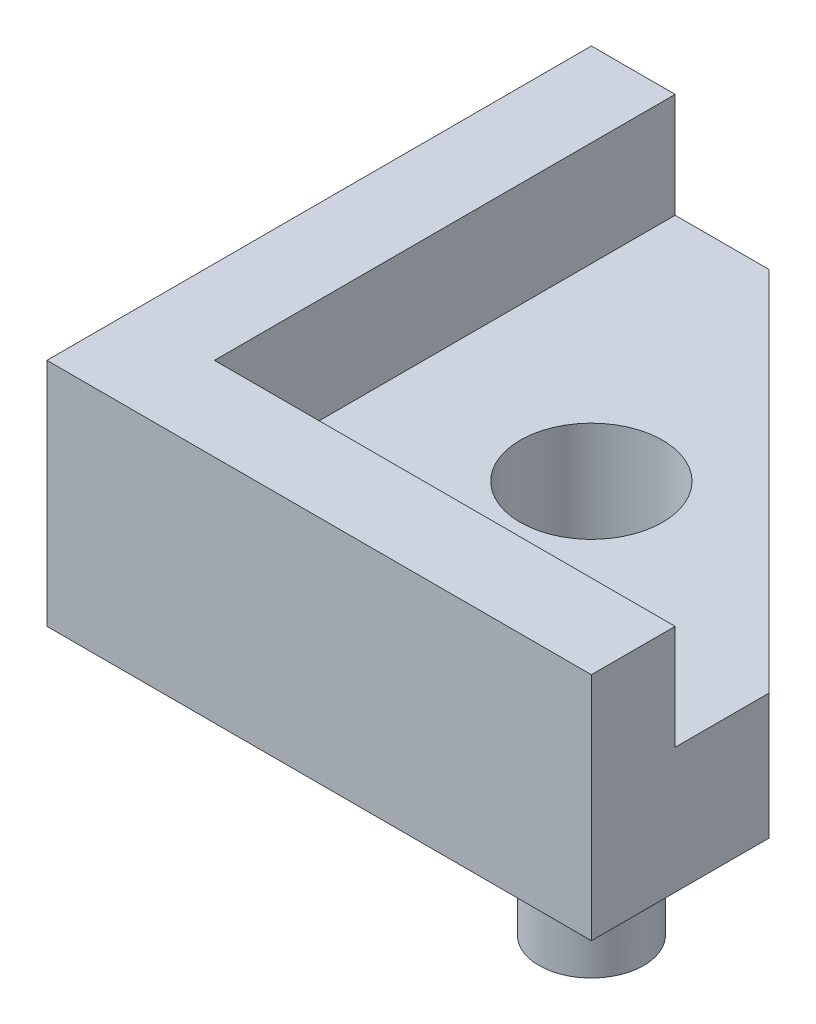
SolidWorks part; units mm, degrees
ref_plane "Front Plane" through (0, 0, 0) normal (0, 0, 1) x (1, 0, 0)
ref_plane "Top Plane" through (0, 0, 0) normal (0, 1, 0) x (1, 0, 0)
ref_plane "Right Plane" through (0, 0, 0) normal (1, 0, 0) x (0, 0, -1)
sketch "Board" plane through (0, 0, 0) normal (0, 1, 0) x (1, 0, 0)
  line L8 (0, 0) -> (85, 0) construction
  line L9 (0, 0) -> (0, 85) construction
  line L10 (0, 85) -> (85, 85) construction
  line L11 (85, 0) -> (85, 85) construction
  circle A1 centre (4, 4) radius 1.6 construction
  point P10 (8.1166, 0)
  dimension "D3" = 3.2
  dimension "D1" = 85
  dimension "D2" = 85
  dimension "D4" = 4
  dimension "D5" = 4
sketch "Sketch3" plane through (0, 0, 0) normal (0, 1, 0) x (1, 0, 0)
  line L0 (-2.5, 10.5) -> (-2.5, -2.5)
  line L1 (-2.5, -2.5) -> (10.5, -2.5)
  line L2 (10.5, -2.5) -> (10.5, 1.7426)
  line L3 (10.5, 1.7426) -> (1.7426, 10.5)
  line L4 (1.7426, 10.5) -> (-2.5, 10.5)
  line L5 (0, 0) -> (0, 85) construction
  line L6 (0, 0) -> (85, 0) construction
  point P2 (-2.7933, 11.3617)
  point P11 (-2, 13)
  dimension "D1" = 2.5
  dimension "D2" = 2.5
  dimension "D3" = 45
  dimension "D4" = 13
  dimension "D5" = 13
  dimension "D6" = 3
extrude "Boss-Extrude2" add sketch "Sketch3" against normal blind 3
sketch "Sketch4" plane through (0, -3, 0) normal (0, -1, 0) x (1, 0, 0)
  line L2 (0.1109, -7.8891) -> (7.8891, -0.1109) construction
  line L3 (10.5, -1.7426) -> (1.7426, -10.5) construction
  circle A0 centre (7.8891, -0.1109) radius 1.25
  circle A1 centre (0.1109, -7.8891) radius 1.25
  dimension "D1" = 2.5
  dimension "D2" = 11
extrude "Boss-Extrude3" add sketch "Sketch4" along normal blind 2.5
sketch "Sketch5" plane through (0, 0, 0) normal (0, 1, 0) x (1, 0, 0)
  line L0 (-2.5, 10.5) -> (-2.5, -2.5)
  line L1 (-2.5, -2.5) -> (10.5, -2.5)
  line L2 (10.5, -2.5) -> (10.5, -0.5)
  line L3 (10.5, -2.5) -> (10.5, 1.7426) construction
  line L4 (10.5, -0.5) -> (-0.5, -0.5)
  line L5 (-0.5, -0.5) -> (-0.5, 10.5)
  line L7 (-0.5, 10.5) -> (-2.5, 10.5)
  line L9 (0, 0) -> (0, 85) construction
  line L10 (0, 0) -> (85, 0) construction
  dimension "D1" = 0.5
  dimension "D2" = 0.5
extrude "Boss-Extrude4" add sketch "Sketch5" along normal blind 2.5
sketch "Sketch6" plane through (0, 0, 0) normal (0, 1, 0) x (1, 0, 0)
  circle A0 centre (4, 4) radius 1.7
  dimension "D1" = 3.4
extrude "Cut-Extrude1" cut sketch "Sketch6" against normal up to next
